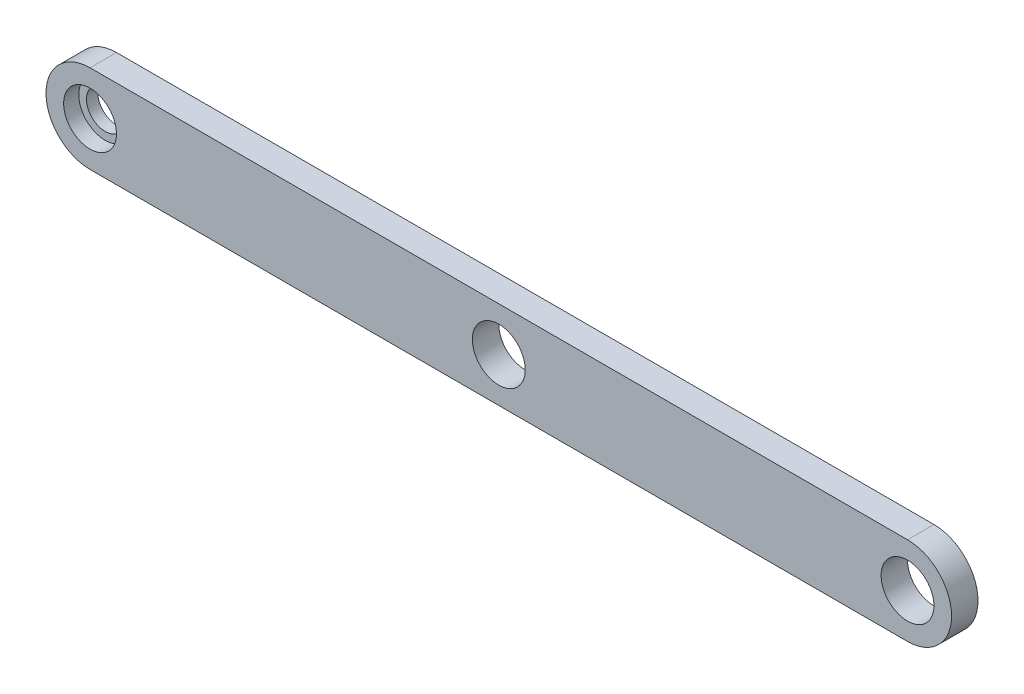
SolidWorks part; units mm, degrees
material "ALUMINUM 6061"
ref_plane "Front Plane" through (0, 0, 0) normal (0, 0, 1) x (1, 0, 0)
ref_plane "Top Plane" through (0, 0, 0) normal (0, 1, 0) x (1, 0, 0)
ref_plane "Right Plane" through (0, 0, 0) normal (1, 0, 0) x (0, 0, -1)
sketch "Sketch1" plane through (0, 0, 0) normal (0, 0, 1) x (1, 0, 0)
  line L0 (-73.66, 0) -> (73.66, 0) construction
  line L1 (-73.66, 7.9375) -> (73.66, 7.9375)
  line L2 (-73.66, -7.9375) -> (73.66, -7.9375)
  arc A0 (-73.66, 7.9375) -> (-73.66, -7.9375) centre (-73.66, 0) ccw
  arc A1 (73.66, -7.9375) -> (73.66, 7.9375) centre (73.66, 0) ccw
  circle A2 centre (73.66, 0) radius 4.7625
  circle A3 centre (-73.66, 0) radius 4.7625
  circle A4 centre (0, 0) radius 4.7625
  circle A5 centre (-73.66, 0) radius 3.3734
  point P2 (0, 0)
  dimension "D3" = 9.525
  dimension "D4" = 6.7469
  dimension "D1" = 15.875
  dimension "D2" = 147.32
extrude "Boss-Extrude1" add sketch "Sketch1" along normal blind 4.7625 contours L2 A1 L1 A0 A3 A4 A2 region at (0, 6.2978, 0)
extrude "Boss-Extrude2" add sketch "Sketch1<2>" along normal blind 2.032 contours A5 | A3 region at (-73.66, 0, 0)
sketch "Sketch1<2>" plane through (0, 0, 0) normal (0, 0, 1) x (1, 0, 0) same geometry as "Sketch1"
move or copy body "Body-Move/Copy1" [suppressed] bodies to move or copy 101
equation "\"D4@Sketch1\"=17/64"
